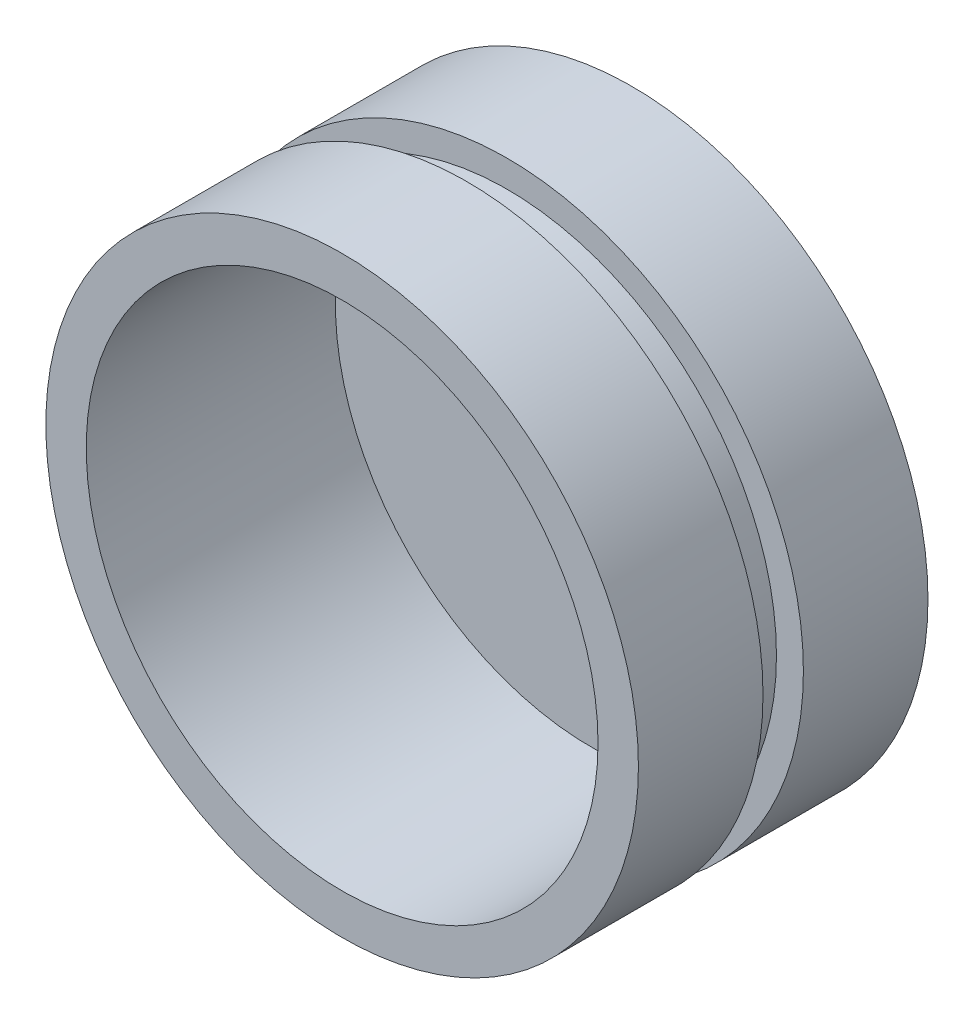
SolidWorks part; units mm, degrees
ref_plane "Front Plane" through (0, 0, 0) normal (0, 0, 1) x (1, 0, 0)
ref_plane "Top Plane" through (0, 0, 0) normal (0, 1, 0) x (1, 0, 0)
ref_plane "Right Plane" through (0, 0, 0) normal (1, 0, 0) x (0, 0, -1)
sketch "Sketch1" plane through (0, 0, 0) normal (0, 0, 1) x (1, 0, 0)
  circle A0 centre (0, 0) radius 22
  circle A1 centre (0, 0) radius 2
  dimension "D1" = 44
  dimension "D2" = 4
extrude "Boss-Extrude1" add sketch "Sketch1" along normal blind 21.5
sketch "Sketch2" plane through (0, 0, 21.5) normal (0, 0, 1) x (1, 0, 0)
  circle A0 centre (0, 0) radius 19
  circle A1 centre (0, 0) radius 22 construction
  dimension "D1" = 3
extrude "Cut-Extrude1" cut sketch "Sketch2" against normal offset from surface (18.5 mm away) 3 up to face at (22, 0, 0)
ref_plane "Plane1" through (0, 0, 10.75) normal (0, 0, 1) x (1, 0, 0)
sketch "Sketch3" plane through (0, 0, 10.75) normal (0, 0, 1) x (1, 0, 0)
  circle A0 centre (0, 0) radius 22 construction
  circle A1 centre (0, 0) radius 22
  circle A2 centre (0, 0) radius 20
  dimension "D1" = 2
extrude "Cut-Extrude2" cut sketch "Sketch3" against normal mid plane 3
